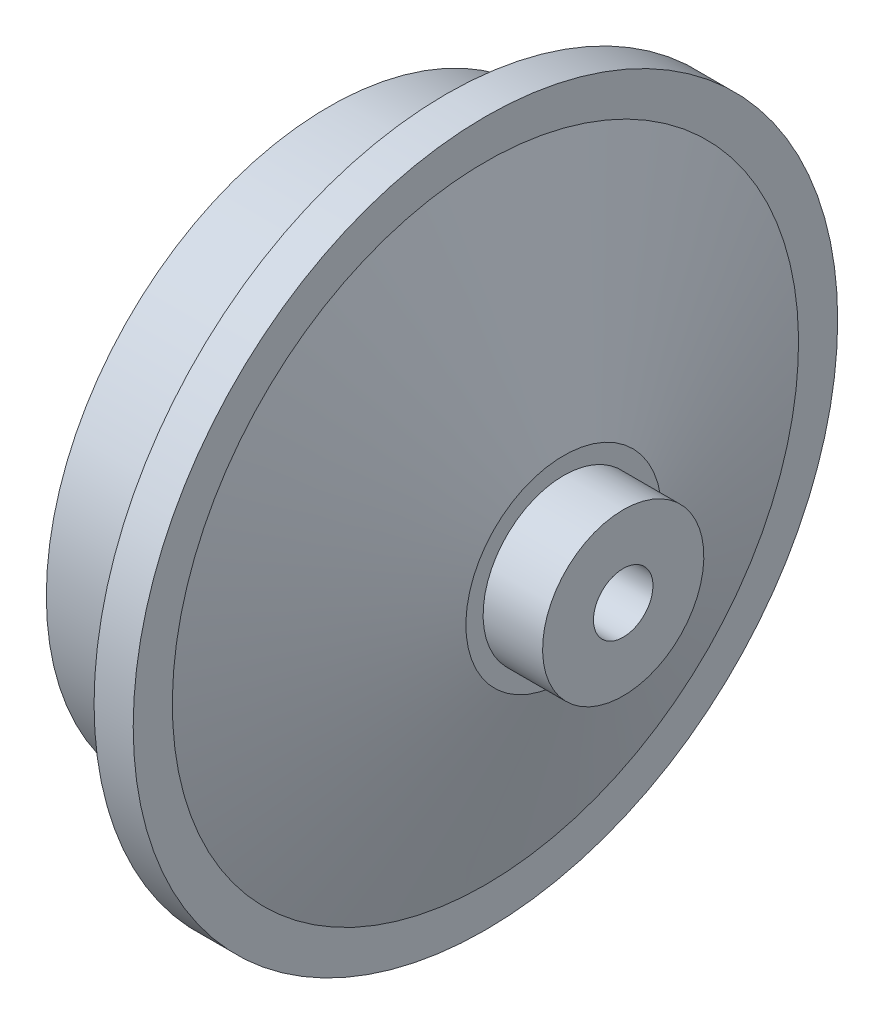
SolidWorks part; units mm, degrees
material "7075-T6 (SN)"
ref_plane "Front Plane" through (0, 0, 0) normal (0, 0, 1) x (1, 0, 0)
ref_plane "Top Plane" through (0, 0, 0) normal (0, 1, 0) x (1, 0, 0)
ref_plane "Right Plane" through (0, 0, 0) normal (1, 0, 0) x (0, 0, -1)
sketch "Sketch1" plane through (0, 0, 0) normal (1, 0, 0) x (0, 0, -1)
  circle A0 centre (0, 0) radius 57.15
  dimension "D1" = 114.3
extrude "Boss-Extrude1" add sketch "Sketch1" along normal blind 6.35
sketch "Sketch2" plane through (0, 0, 0) normal (-1, 0, 0) x (0, 0, 1)
  circle A0 centre (0, 0) radius 45.847
  dimension "D1" = 91.694
extrude "Boss-Extrude2" add sketch "Sketch2" along normal blind 19.05
sketch "Sketch3" plane through (-19.05, 0, 0) normal (-1, 0, 0) x (0, 0, 1)
  circle A0 centre (0, 0) radius 38.227
  dimension "D1" = 76.454
extrude "Cut-Extrude1" cut sketch "Sketch3" against normal blind 6.604
sketch "Sketch5" plane through (0, 0, 0) normal (0, 0, 1) x (1, 0, 0)
  line L0 (6.35, -50.8) -> (19.05, -15.875)
  line L1 (6.35, -57.15) -> (6.35, 57.15) construction
  line L2 (6.35, 0) -> (19.05, 0)
  line L3 (19.05, 0) -> (19.05, -15.875)
  line L4 (6.35, -50.8) -> (6.35, 0)
  dimension "D1" = 50.8
  dimension "D2" = 15.875
  dimension "D3" = 12.7
revolve "Revolve1" add sketch "Sketch5" angle 360 about L2
sketch "Sketch6" plane through (19.05, 0, 0) normal (1, 0, 0) x (0, 0, -1)
  circle A0 centre (0, 0) radius 13.081
  dimension "D1" = 26.162
extrude "Boss-Extrude3" add sketch "Sketch6" along normal blind 9.652
sketch "Sketch7" plane through (28.702, 0, 0) normal (1, 0, 0) x (0, 0, -1)
  circle A0 centre (0, 0) radius 4.826
  dimension "D1" = 9.652
extrude "Cut-Extrude2" cut sketch "Sketch7" against normal through all
sketch "Sketch8" plane through (0, 0, 0) normal (0, 0, 1) x (1, 0, 0)
  line L0 (0, 0) -> (-12.446, 0)
  line L1 (-12.446, 38.227) -> (-12.446, -38.227) construction
  line L2 (-12.446, 0) -> (-12.446, -29.21)
  line L4 (10.414, 0) -> (0, 0)
  line L6 (10.414, -15.875) -> (10.414, 0)
  line L7 (-12.446, -29.21) -> (-2.794, -29.21)
  line L8 (-2.794, -29.21) -> (10.414, -15.875)
  dimension "D1" = 29.21
  dimension "D2" = 12.446
  dimension "D3" = 15.875
  dimension "D4" = 10.414
  dimension "D5" = 9.652
revolve "Cut-Revolve2" cut sketch "Sketch8" angle 360 about L4
fillet "Fillet1" radius 2.032 2 edges at (-2.794, 29.21, 0) (10.414, 15.875, 0)
